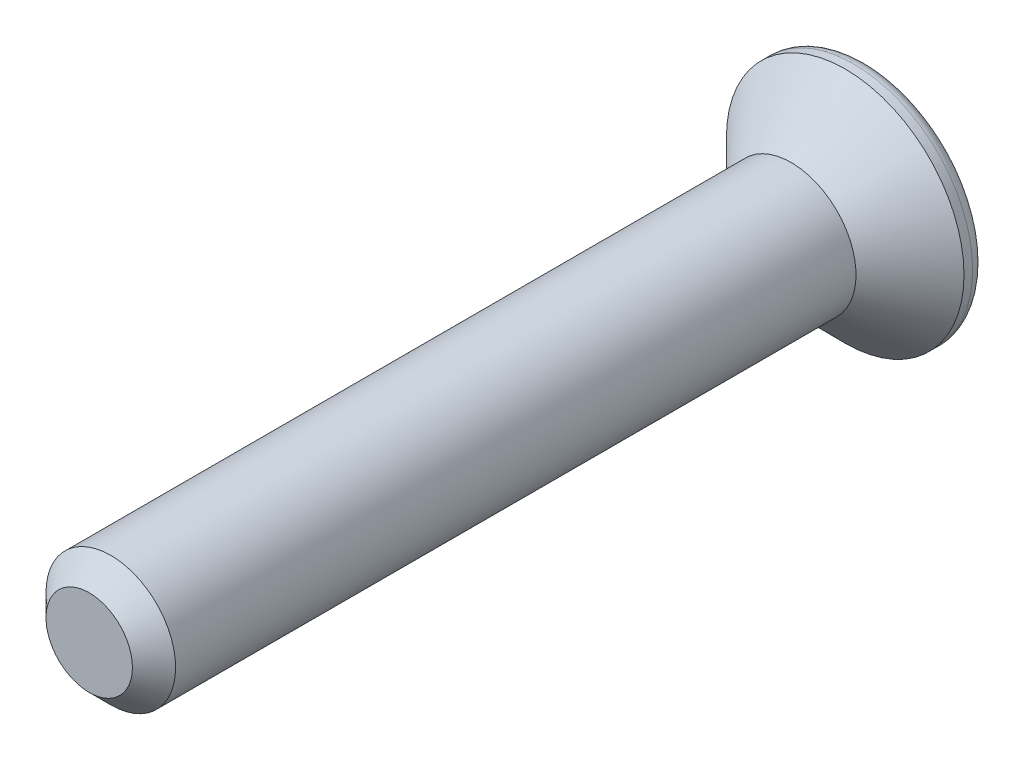
SolidWorks part; units mm, degrees
ref_plane "Front Plane" through (0, 0, 0) normal (0, 0, 1) x (1, 0, 0)
ref_plane "Top Plane" through (0, 0, 0) normal (0, 1, 0) x (1, 0, 0)
ref_plane "Right Plane" through (0, 0, 0) normal (1, 0, 0) x (0, 0, -1)
sketch "Sketch1" plane through (0, 0, 0) normal (0, 0, 1) x (1, 0, 0)
  circle A0 centre (0, 0) radius 2.75
  dimension "D1" = 5.5
extrude "Boss-Extrude1" add sketch "Sketch1" along normal blind 2
sketch "Sketch2" plane through (0, 0, 2) normal (0, 0, 1) x (1, 0, 0)
  circle A0 centre (0, 0) radius 1.5
  point P2 (0, 0)
  dimension "D1" = 3
extrude "Boss-Extrude2" add sketch "Sketch2" along normal blind 16
chamfer "Chamfer1" distance 1.5 angle 45 1 edges at (2.75, 0, 2)
fillet "Fillet1" radius 0.3 1 edges at (2.75, 0, 0)
chamfer "Chamfer2" distance 0.5 angle 45 1 edges at (1.5, 0, 18)
sketch "Sketch3" plane through (0, 0, 0) normal (0, 0, -1) x (-1, 0, 0)
  line L1 (0, -1.4434) -> (1.25, -0.7217)
  line L2 (1.25, -0.7217) -> (1.25, 0.7217)
  line L3 (1.25, 0.7217) -> (0, 1.4434)
  line L4 (0, 1.4434) -> (-1.25, 0.7217)
  line L5 (-1.25, 0.7217) -> (-1.25, -0.7217)
  line L6 (-1.25, -0.7217) -> (0, -1.4434)
  circle A0 centre (0, 0) radius 1.25 construction
  dimension "D1" = 2.5
extrude "Cut-Extrude1" cut sketch "Sketch3" against normal blind 2
fillet "Fillet2" radius 0.3 6 edges at (0.625, -1.0825, 0) (-0.625, -1.0825, 0) (-1.25, 0, 0) (-0.625, 1.0825, 0) (0.625, 1.0825, 0) (1.25, 0, 0)
